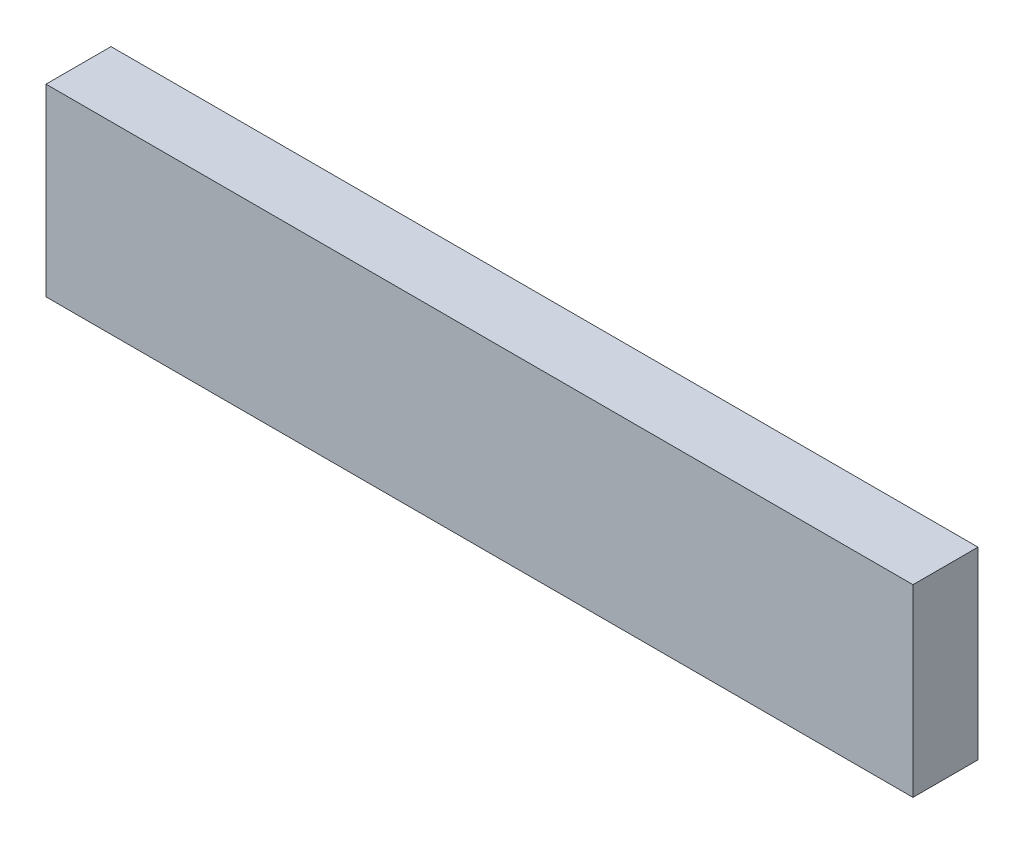
SolidWorks part; units mm, degrees
ref_plane "Ön Düzlem" through (0, 0, 0) normal (0, 0, 1) x (1, 0, 0)
ref_plane "Üst Düzlem" through (0, 0, 0) normal (0, 1, 0) x (1, 0, 0)
ref_plane "Sağ Düzlem" through (0, 0, 0) normal (1, 0, 0) x (0, 0, -1)
sketch "Çizim1" plane through (0, 0, 0) normal (0, 0, 1) x (1, 0, 0)
  line L1 (0, 0) -> (400, 0)
  line L2 (0, 0) -> (0, -85)
  line L3 (0, -85) -> (400, -85)
  line L4 (400, 0) -> (400, -85)
  dimension "D1" = 400
  dimension "D2" = 85
base flange "Taban-Flanş1" sketch "Çizim1" thickness 30 reverse thickness direction no parameters "D1"=4
sketch "Büküm-Çizgileri1" [suppressed] plane through (0, 0, 0) normal (0, 1, 0) x (1, 0, 0)
sketch "Sınırlandırma-Kutusu1" [suppressed] plane through (0, 0, 0) normal (0, 1, 0) x (1, 0, 0)
sheet metal parameters "Sac-Levha1" thickness 30 parameters "D1"=4
flat pattern "Düz-Çoğaltma1" [suppressed]
sketch "Büküm-Çizgileri2" plane through (0, 0, 0) normal (0, 1, 0) x (1, 0, 0)
sketch3d "Sınırlandırma-Kutusu2" [suppressed]
  line L0 (0, -85, 0) -> (400, -85, 0) construction
  line L1 (0, 0, 0) -> (400, 0, 0) construction
  line L2 (0, -85, 0) -> (0, 0, 0) construction
  line L3 (400, -85, 0) -> (400, 0, 0) construction
